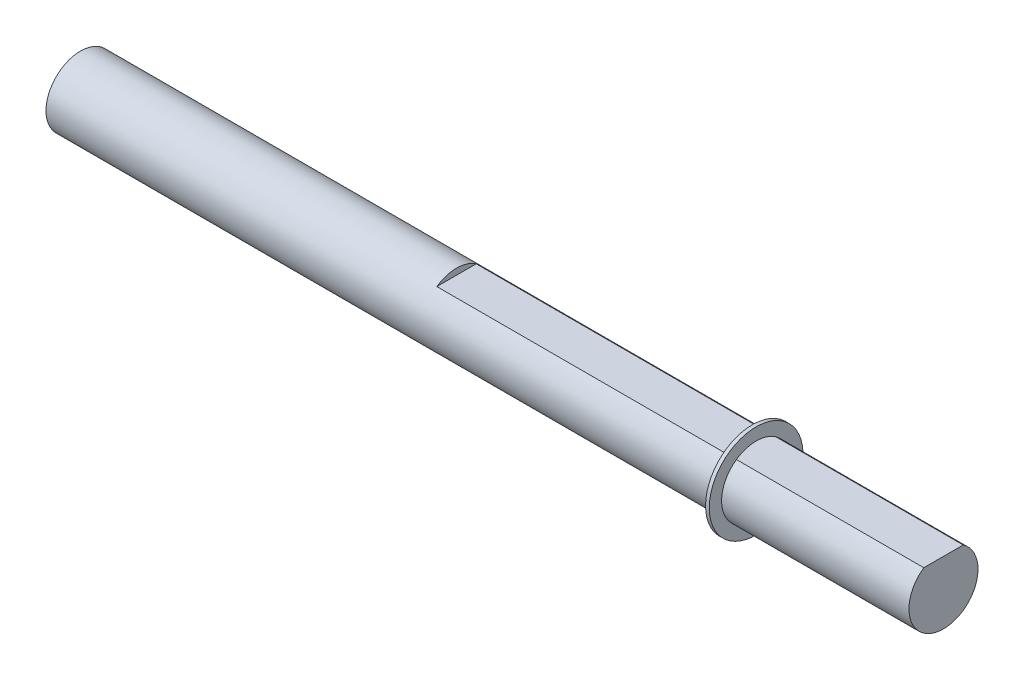
SolidWorks part; units mm, degrees
ref_plane "Plan de face" through (0, 0, 0) normal (0, 0, 1) x (1, 0, 0)
ref_plane "Plan de dessus" through (0, 0, 0) normal (0, 1, 0) x (1, 0, 0)
ref_plane "Plan de droite" through (0, 0, 0) normal (1, 0, 0) x (0, 0, -1)
sketch "Esquisse1" plane through (0, 0, 0) normal (0, 0, 1) x (1, 0, 0)
  line L0 (54.8, 2.8) -> (54.8, 3.8)
  line L1 (0, 0) -> (70, 0)
  line L2 (0, 0) -> (0, 2.8)
  line L3 (0, 2.8) -> (54.5, 2.8)
  line L4 (70, 0) -> (70, 2.8)
  line L5 (54.8, 3.8) -> (54.5, 3.8)
  line L6 (54.5, 3.8) -> (54.5, 2.8)
  line L7 (54.8, 2.8) -> (70, 2.8)
  dimension "D1" = 70
  dimension "D2" = 2.8
  dimension "D3" = 15.5
  dimension "D4" = 0.3
  dimension "D5" = 1
revolve "Révolution1" add sketch "Esquisse1" angle 360 about L1
sketch "Esquisse2" plane through (70, 0, 0) normal (1, 0, 0) x (0, 0, -1)
  line L0 (-1.5969, 2.3) -> (1.5969, 2.3)
  line L1 (-1.3775, -2.8) -> (1.8305, -2.8) construction
  circle A0 centre (0, 0) radius 2.8 construction
  arc A1 (1.5969, 2.3) -> (-1.5969, 2.3) centre (0, 0) ccw
  circle A2 centre (0, 0) radius 2.8 construction
  dimension "D1" = 5.1
extrude "Enlèv. mat.-Extru.1" cut sketch "Esquisse2" against normal offset from surface (39.5 mm away) 30.5 up to face at (0, 0, 2.8)
